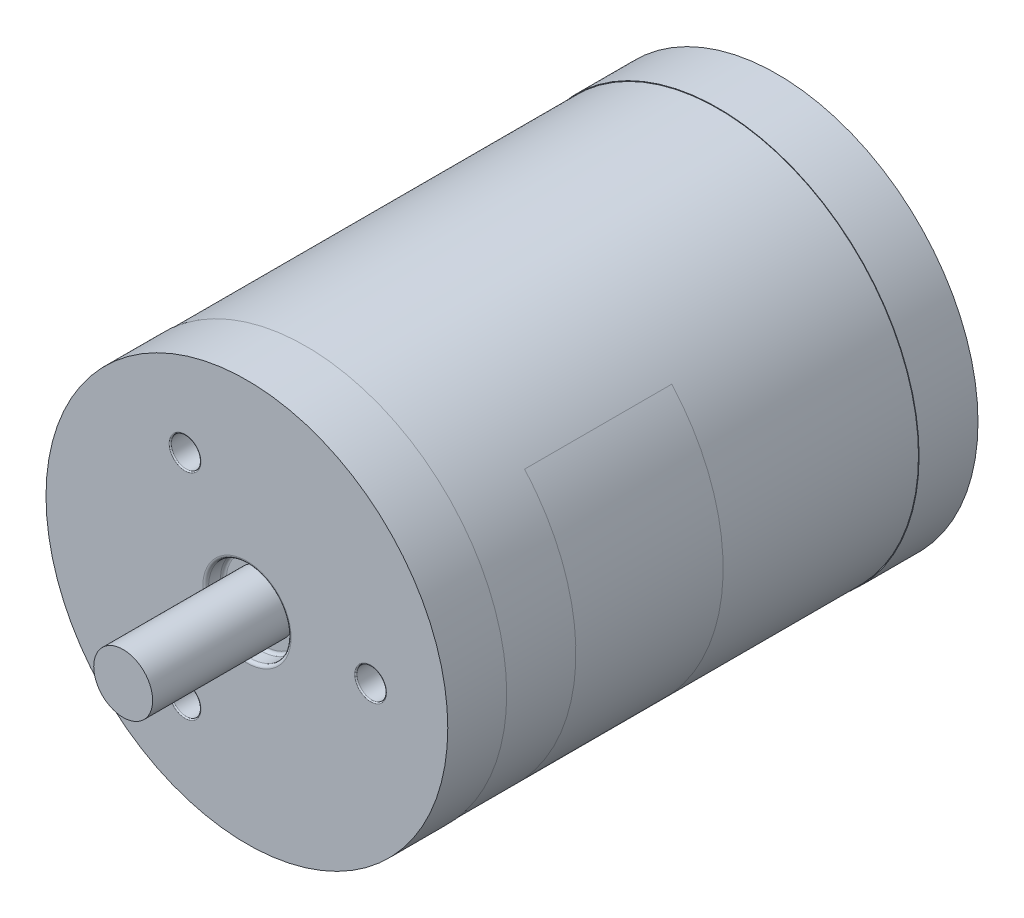
SolidWorks part; units mm, degrees
ref_plane "Alzado" through (0, 0, 0) normal (0, 0, 1) x (1, 0, 0)
ref_plane "Planta" through (0, 0, 0) normal (0, 1, 0) x (1, 0, 0)
ref_plane "Vista lateral" through (0, 0, 0) normal (1, 0, 0) x (0, 0, -1)
sketch "Croquis1" plane through (0, 0, 0) normal (0, 0, 1) x (1, 0, 0)
  circle A0 centre (0, 0) radius 34
  dimension "D1" = 68
extrude "Saliente-Extruir1" add sketch "Croquis1" along normal mid plane 90
sketch "Croquis2" plane through (0, 0, 45) normal (0, 0, 1) x (1, 0, 0)
  circle A0 centre (0, 0) radius 5
  dimension "D1" = 10
extrude "Saliente-Extruir2" add sketch "Croquis2" along normal blind 21
sketch "Croquis3" plane through (0, 0, 45) normal (0, 0, 1) x (1, 0, 0)
  circle A0 centre (0, 0) radius 21 construction
  circle A1 centre (21, 0) radius 2.5
  circle A2 centre (-10.5, -18.1865) radius 2.5
  circle A3 centre (-10.5, 18.1865) radius 2.5
  point P12 (0, 0)
  dimension "D1" = 42
  dimension "D2" = 5
  dimension "D4" = 36.3731
  dimension "D5" = 36.3731
  dimension "D3" = 3
extrude "Cortar-Extruir1" cut sketch "Croquis3" against normal blind 5
sketch "Croquis4" plane through (0, 0, -45) normal (0, 0, -1) x (-1, 0, 0)
  circle A0 centre (0, 0) radius 15
  dimension "D1" = 30
extrude "Saliente-Extruir3" add sketch "Croquis4" along normal blind 10.5
sketch "Croquis5" plane through (0, 0, -45) normal (0, 0, -1) x (-1, 0, 0)
  line L0 (-30, 0) -> (0, 0) construction
  circle A0 centre (-30, 0) radius 2
  circle A1 centre (0, 0) radius 30 construction
  circle A2 centre (30, 0) radius 2
  dimension "D1" = 4
  dimension "D2" = 60
extrude "Cortar-Extruir2" cut sketch "Croquis5" against normal blind 10.5
sketch "Croquis6" plane through (0, 0, 45) normal (0, 0, 1) x (1, 0, 0)
  circle A0 centre (0, 0) radius 34.1
  circle A1 centre (0, 0) radius 34 construction
  circle A2 centre (21, 0) radius 2.5 construction
  circle A3 centre (-10.5, -18.1865) radius 2.5 construction
  circle A4 centre (-10.5, 18.1865) radius 2.5 construction
  circle A5 centre (21, 0) radius 2.5
  circle A6 centre (-10.5, -18.1865) radius 2.5
  circle A7 centre (-10.5, 18.1865) radius 2.5
  dimension "D1" = 0.1
extrude "Saliente-Extruir4" add sketch "Croquis6" against normal blind 10
mirror "Simetría1" about plane through (0, 0, 0) normal (0, 0, 1) of "Saliente-Extruir4"
fillet "Redondeo1" radius 1 1 edges at (-15, 0, -55.5)
sketch "Croquis7" plane through (0, 0, 0) normal (1, 0, 0) x (0, 0, -1)
  line L1 (-23.1573, -24.8743) -> (1.8427, -24.8743)
  line L2 (-23.1573, -24.8743) -> (-23.1573, 24.8743)
  line L3 (-23.1573, 24.8743) -> (1.8427, 24.8743)
  line L4 (1.8427, -24.8743) -> (1.8427, 24.8743)
  line L5 (-23.1573, -24.8743) -> (1.8427, 24.8743) construction
  line L6 (-23.1573, 24.8743) -> (1.8427, -24.8743) construction
  point P0 (-10.6573, 0)
  dimension "D1" = 25
wrap "Envolver1" sketch "Croquis7" wrap type scribe source sketch "Croquis7" face at (34, 0, 35)
ref_plane "Plano1" through (0, -34, 0) normal (0, -1, 0) x (-1, 0, 0)
sketch "Croquis8" plane through (0, -34, 0) normal (0, -1, 0) x (-1, 0, 0)
  line L1 (9.3304, -43.5501) -> (-9.3304, -43.5501)
  line L2 (9.3304, -43.5501) -> (9.3304, -33.5047)
  line L3 (9.3304, -33.5047) -> (-9.3304, -33.5047)
  line L4 (-9.3304, -43.5501) -> (-9.3304, -33.5047)
  line L5 (9.3304, -43.5501) -> (-9.3304, -33.5047) construction
  line L6 (9.3304, -33.5047) -> (-9.3304, -43.5501) construction
  point P0 (0, -38.5274)
extrude "Cortar-Extruir3" cut sketch "Croquis8" against normal blind 5 and the other way blind 5
sketch "Croquis9" plane through (0, 0, -45) normal (0, 0, -1) x (-1, 0, 0)
  circle A1 centre (30, 0) radius 2
  circle A2 centre (30, 0) radius 2
  circle A3 centre (-30, 0) radius 2
  circle A4 centre (-30, 0) radius 2
  dimension "D1" = 0
  dimension "D2" = 0
extrude "Cortar-Extruir4" cut sketch "Croquis9" against normal blind 5
sketch "Croquis10" plane through (0, 0, 45) normal (0, 0, 1) x (1, 0, 0)
  circle A0 centre (0, 0) radius 5 construction
  circle A1 centre (0, 0) radius 5
  circle A2 centre (0, 0) radius 7
  dimension "D1" = 2
extrude "Cortar-Extruir5" cut sketch "Croquis10" against normal blind 3
fillet "Redondeo2" radius 0.5 1 edges at (7, 0, 45)
fillet "Redondeo3" radius 0.5 1 edges at (7, 0, 42)
fillet "Redondeo4" radius 0.2 3 edges at (-8, 18.1865, 45) (23.5, 0, 45) (-8, -18.1865, 45)
